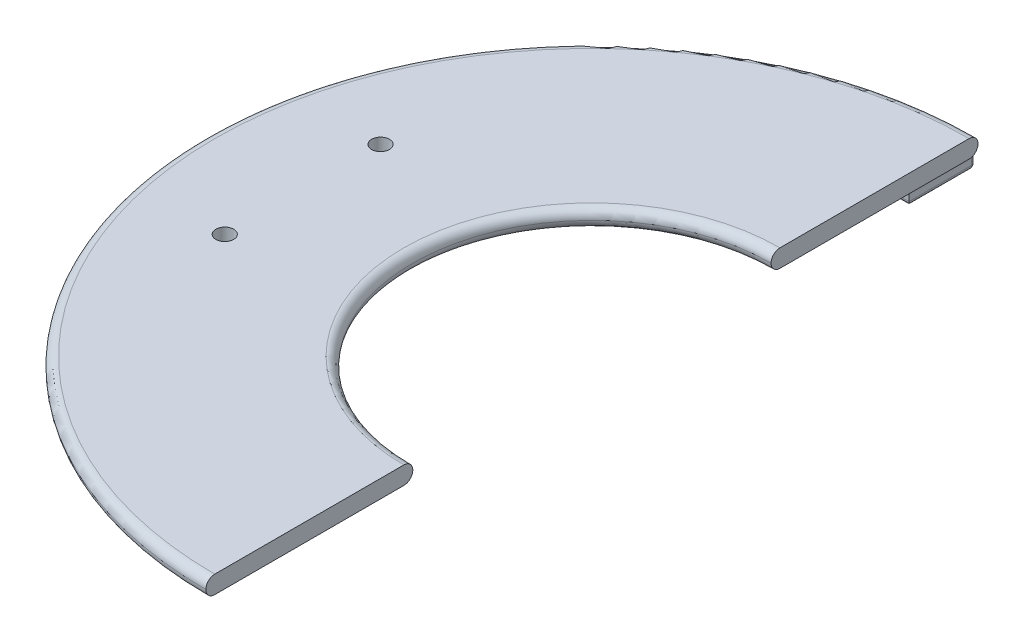
SolidWorks part; units mm, degrees
ref_plane "Front Plane" through (0, 0, 0) normal (0, 0, 1) x (1, 0, 0)
ref_plane "Top Plane" through (0, 0, 0) normal (0, 1, 0) x (1, 0, 0)
ref_plane "Right Plane" through (0, 0, 0) normal (1, 0, 0) x (0, 0, -1)
sketch "Sketch1" plane through (0, 0, 0) normal (0, 1, 0) x (1, 0, 0)
  line L0 (0, 86.75) -> (0, 40.25)
  line L1 (0, -40.25) -> (0, -86.75)
  arc A0 (0, 40.25) -> (0, -40.25) centre (0, 0) ccw
  arc A1 (0, 86.75) -> (0, -86.75) centre (0, 0) ccw
  dimension "D1" = 173.5
  dimension "D2" = 80.5
extrude "Boss-Extrude1" add sketch "Sketch1" along normal blind 4
sketch "Sketch2" plane through (0, 0, 0) normal (0, -1, 0) x (1, 0, 0)
  line L1 (-2.5, -83.75) -> (-14.5, -83.75)
  line L2 (-2.5, -83.75) -> (-2.5, -73.75)
  line L3 (-2.5, -73.75) -> (-14.5, -73.75)
  line L4 (-14.5, -83.75) -> (-14.5, -73.75)
  line L5 (0, -40.25) -> (0, -86.75) construction
  dimension "D1" = 12
  dimension "D2" = 10
  dimension "D3" = 3
  dimension "D4" = 2.5
extrude "Boss-Extrude2" add sketch "Sketch2" along normal blind 5
sketch "Sketch3" plane through (0, 0, -83.75) normal (0, 0, -1) x (-1, 0, 0)
  line L1 (2.5, -5) -> (14.5, -5)
  line L2 (2.5, -5) -> (2.5, -1.5)
  line L3 (2.5, -1.5) -> (14.5, -1.5)
  line L4 (14.5, -5) -> (14.5, -1.5)
  line L5 (14.5, -5) -> (14.5, 0) construction
  dimension "D1" = 3.5
extrude "Boss-Extrude3" add sketch "Sketch3" along normal blind 5
fillet "Fillet1" radius 1 9 edges at (-14.5, -5, -81.25) (-2.5, -5, -81.25) (-2.5, -1.5, -86.25) (-14.5, -1.5, -86.25) (-8.5, -5, -73.75) (-8.5, -5, -88.75) (-8.5, -1.5, -88.75) (-14.5, -3.25, -88.75) (-2.5, -3.25, -88.75)
fillet "Fillet2" radius 2 4 edges at (-86.75, 4, 0) (-40.25, 0, 0) (-86.75, 0, 0) (-40.25, 4, 0)
sketch "Sketch4" plane through (0, 4, 0) normal (0, 1, 0) x (1, 0, 0)
  line L0 (0, 0) -> (-65, 0) construction
  line L1 (-65, -17.5) -> (-65, 17.5) construction
  circle A0 centre (-65, -17.5) radius 2
  circle A1 centre (-65, 17.5) radius 2
  point P5 (-65, 0)
  dimension "D1" = 35
  dimension "D2" = 65
hole_wizard "Ø4.0mm Dowel Hole1" positions "3DSketch1" profile "Sketch5" hole size "Ø4.0" standard "ANSI Metric" end condition through all
sketch3d "3DSketch1"
  point P0 (-65, 4, 17.5)
  point P3 (-65, 4, -17.5)
sketch "Sketch5" plane through (-65, 4, 17.5) normal (1, 0, 0) x (0, 0, 1)
  line L0 (0, 0) -> (0, 9)
  line L1 (0, 9) -> (2, 9)
  line L2 (2, 9) -> (2, 0)
  line L5 (2, 0) -> (0, 0)
  line L11 (0, -6.35) -> (0, 107.95) construction
  dimension "Thru Hole Dia." = 4
  dimension "Thru Hole Depth" = 9
